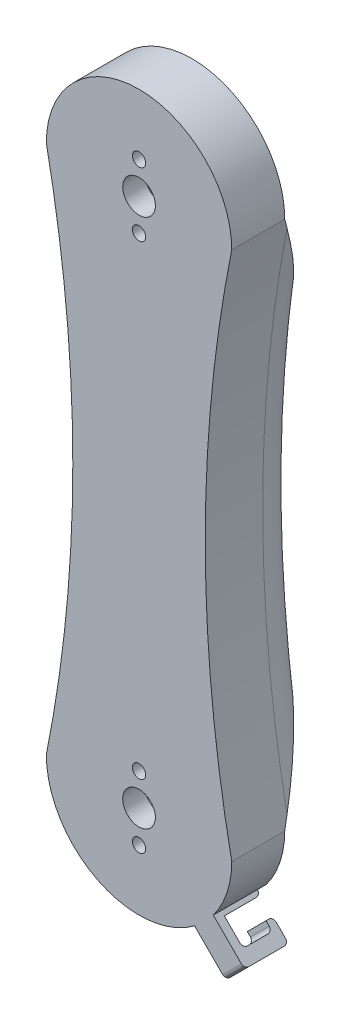
SolidWorks part; units mm, degrees
ref_plane "Front Plane" through (0, 0, 0) normal (0, 0, 1) x (1, 0, 0)
ref_plane "Top Plane" through (0, 0, 0) normal (0, 1, 0) x (1, 0, 0)
ref_plane "Right Plane" through (0, 0, 0) normal (1, 0, 0) x (0, 0, -1)
sketch "Sketch1" plane through (0, 0, 0) normal (0, 0, 1) x (1, 0, 0)
  line L0 (-14.2575, 153.4115) -> (-14.2597, 138.9115) construction
  line L1 (0, -60) -> (40.9433, -100.9433) construction
  line L2 (0, -60) -> (21, -60) construction
  line L3 (23.8893, -79.6467) -> (19.6467, -83.8893)
  line L4 (-43.384, 85.7461) -> (-13.4447, 85.742) construction
  line L5 (23.8893, -79.6467) -> (16.8183, -72.5756)
  line L6 (0, 60) -> (0, -60) construction
  line L7 (-15, 0) -> (15, 0)
  line L8 (19.6467, -83.8893) -> (12.5756, -76.8183)
  circle A2 centre (-14.2575, 153.4115) radius 1.5
  circle A4 centre (-14.2597, 138.9115) radius 1.5
  circle A5 centre (-28.4819, 146.1615) radius 3.7
  arc A9 (-44.4338, 115.2289) -> (-43.384, 85.7461) centre (-511.1209, 83.8506) cw
  arc A10 (-48.6297, 140.2399) -> (-44.4338, 115.2289) centre (-172.3352, 106.6293) cw
  arc A11 (-8.315, 140.3053) -> (-48.6297, 140.2399) centre (-28.4819, 146.1615) ccw
  arc A12 (-8.315, 140.3053) -> (-12.4298, 115.2808) centre (115.4988, 107.096) ccw
  arc A13 (-12.4298, 115.2808) -> (-13.384, 85.7947) centre (454.3567, 85.4161) ccw
  arc A14 (21, 60) -> (-21, 60) centre (0, 60) ccw
  circle A15 centre (0, -52.75) radius 1.5
  circle A16 centre (0, -67.25) radius 1.5
  circle A17 centre (0, -60) radius 3.7
  arc A18 (21, -60) -> (16.8183, -72.5756) centre (0, -60) cw
  circle A19 centre (0, 60) radius 3.7
  circle A20 centre (0, 67.25) radius 1.5
  circle A21 centre (0, 52.75) radius 1.5
  arc A22 (21, 60) -> (21, -60) centre (318, 0) ccw
  arc A23 (-21, 60) -> (-21, -60) centre (-318, 0) cw
  arc A24 (12.5756, -76.8183) -> (-21, -60) centre (0, -60) cw
  point P20 (0, 0)
  point P32 (21.768, -81.768)
  point P41 (0, 0)
  point P51 (-10.9927, 127.895)
  dimension "D1" = 7.4
  dimension "D2" = 3
  dimension "D3" = 3
  dimension "D4" = 21
  dimension "D5" = 7.4
  dimension "D6" = 42
  dimension "D7" = 15
  dimension "D8" = 45
  dimension "D10" = 128.1902
  dimension "D11" = 467.7408
  dimension "D21" = 3
  dimension "D22" = 3
  dimension "D9" = 6
  dimension "D12" = 10
  dimension "D13" = 10
  dimension "D15" = 7.25
  dimension "D16" = 14.5
  dimension "D20" = 120
  dimension "D23" = 14.5
  dimension "D25" = 7.25
extrude "Boss-Extrude1" add sketch "Sketch1" along normal blind 12 contours A24 L8 L3 L5 A18 A22 L7 A23 A16 A15 A17 | A14 A23 L7 A22 A19 A20 A21
sketch "Sketch2" plane through (0, 0, 0) normal (0, 0, -1) x (-1, 0, 0)
  circle A0 centre (0, 60) radius 18
  circle A1 centre (0, -60) radius 18
  arc A2 (-12.5756, -76.8183) -> (21, -60) centre (0, -60) ccw construction
  arc A3 (21, 60) -> (-21, 60) centre (0, 60) ccw construction
  dimension "D1" = 3
  dimension "D2" = 3
extrude "Cut-Extrude1" cut sketch "Sketch2" against normal blind 7
sketch "Sketch3" plane through (0, 0, 0) normal (0, 0, -1) x (-1, 0, 0)
  line L0 (-21, 60) -> (-18, 60)
  line L1 (18, 60) -> (21, 60)
  line L2 (-21, -60) -> (-18, -60)
  line L3 (-16.8183, -72.5756) -> (-23.8893, -79.6467)
  line L4 (-23.8893, -79.6467) -> (-19.6467, -83.8893)
  line L5 (-19.6467, -83.8893) -> (-12.5756, -76.8183)
  line L7 (-23.8893, -79.6467) -> (-19.6467, -83.8893)
  line L8 (-19.6467, -83.8893) -> (-12.5756, -76.8183)
  line L9 (18, -60) -> (21, -60)
  circle A0 centre (0, 60) radius 18 construction
  arc A1 (-18, 60) -> (18, 60) centre (0, 60) ccw
  circle A2 centre (0, -60) radius 18 construction
  arc A3 (18, -60) -> (-18, -60) centre (0, -60) ccw
  arc A5 (-12.5756, -76.8183) -> (21, -60) centre (0, -60) ccw
  arc A6 (21, 60) -> (21, -60) centre (318, 0) ccw
  arc A7 (21, 60) -> (-21, 60) centre (0, 60) ccw
  arc A8 (-21, -60) -> (-21, 60) centre (-318, 0) ccw
  arc A9 (-21, -60) -> (-16.8183, -72.5756) centre (0, -60) ccw
  arc A11 (21, 60) -> (21, -60) centre (318, 0) ccw
  arc A13 (-21, -60) -> (-21, 60) centre (-318, 0) ccw
  dimension "D1" = 0
extrude "Boss-Extrude2" add sketch "Sketch3" along normal blind 11 contours L1 L9 L3 L0 L5 L2
fillet "Fillet1" radius 10 8 edges at (-19.5, 60, -11) (19.5, 60, -11) (0, -42, -11) (-19.5, -60, -11) (-15, 0, -11) (0, 42, -11) (15, 0, -11) (19.5, -60, -11)
ref_plane "Plane1" through (3.7, 0, 0) normal (-1, 0, 0) x (0, 0, 1)
sketch "Sketch4" plane through (3.7, 0, 0) normal (-1, 0, 0) x (0, 0, 1)
  line L0 (0, 60) -> (-11, 32.8197)
  line L1 (-11, 32.8197) -> (-11, 60)
  line L2 (-11, 60) -> (0, 60)
  line L3 (0, 0) -> (12.6201, 0) construction
  line L4 (-11, -60) -> (0, -60)
  line L5 (-11, -32.8197) -> (-11, -60)
  line L6 (0, -60) -> (-11, -32.8197)
  line L7 (-1, -60) -> (0, -60) construction
  line L8 (12, -60) -> (0, -60) construction
  dimension "D1" = 11
extrude "Cut-Extrude2" cut sketch "Sketch4" against normal through all both and the other way through all
sketch "Sketch5" plane through (0, 0, 0) normal (0, 1, 0) x (1, 0, 0)
  line L0 (0, -12) -> (0, -4) construction
  line L1 (-21, -12) -> (21, -12) construction
  line L2 (0, -4) -> (0, 3) construction
  circle A0 centre (0, 3) radius 5
  dimension "D3" = 10
  dimension "D1" = 8
  dimension "D2" = 7
extrude "Cut-Extrude3" cut sketch "Sketch5" against normal mid plane 100
sketch "Sketch6" plane through (-27.8787, -27.8787, 0) normal (0.7071, 0.7071, 0) x (0, 0, -1)
  line L0 (0, -63.211) -> (0, -73.211)
  line L1 (-12, -73.211) -> (0, -73.211) construction
  line L2 (0, -73.211) -> (0, -63.211) construction
  line L3 (0, -73.211) -> (-2, -73.211)
  line L4 (-2, -73.211) -> (-2, -63.211)
  line L5 (-12, -63.211) -> (0, -63.211) construction
  line L6 (-2, -63.211) -> (0, -63.211)
  line L7 (-2, -64.211) -> (-10.2, -64.211)
  line L8 (-10.2, -64.211) -> (-10.2, -70.211)
  line L9 (-10.2, -70.211) -> (-3.6, -70.211)
  line L10 (-3.6, -70.211) -> (-3.6, -68.211)
  line L11 (-3.6, -68.211) -> (-2, -68.211)
  line L12 (-12, -73.211) -> (-12, -63.211) construction
  line M6 (0, -73.211) -> (0, -63.211)
  line M7 (0, -63.211) -> (-12, -63.211)
  line M9 (-12, -73.211) -> (0, -73.211)
  dimension "D1" = 2
  dimension "D2" = 6
  dimension "D3" = 1
  dimension "D4" = 1.8
  dimension "D5" = 1.6
extrude "Cut-Extrude4" cut sketch "Sketch6" against normal mid plane 100 contours L10 L11 L4 L7 L8 L9 | L4 M9 M6 M7
fillet "Fillet2" radius 1 6 edges at (19.6467, -79.6467, 10.2) (19.6467, -79.6467, 3.6) (21.768, -81.768, 12) (21.768, -81.768, 2) (15.404, -75.404, 2) (18.2325, -78.2325, 2)
ref_point "Point1"
ref_point "Point2"
